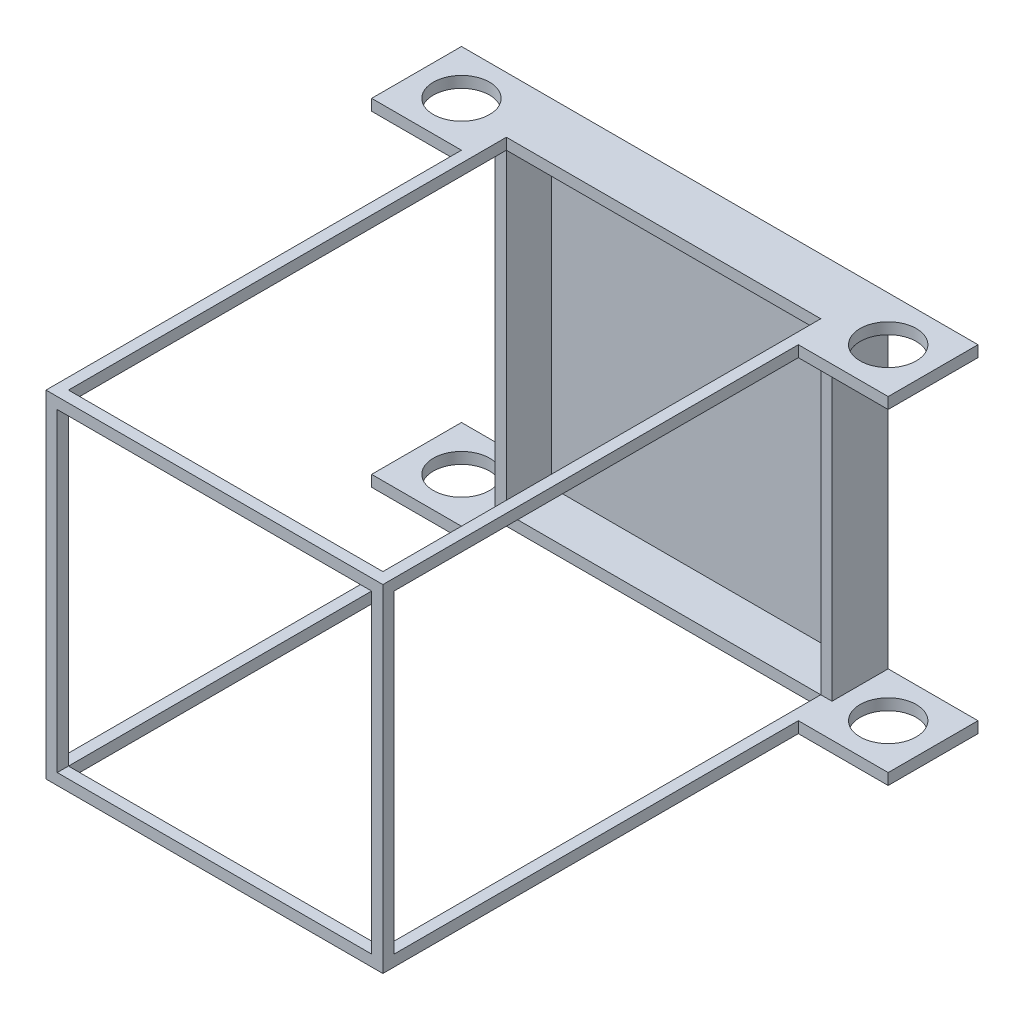
SolidWorks part; units mm, degrees
ref_plane "Спереди" through (0, 0, 0) normal (0, 0, 1) x (1, 0, 0)
ref_plane "Сверху" through (0, 0, 0) normal (0, 1, 0) x (1, 0, 0)
ref_plane "Справа" through (0, 0, 0) normal (1, 0, 0) x (0, 0, -1)
sketch "Эскиз1" plane through (0, 0, 0) normal (0, 0, 1) x (1, 0, 0)
  line L1 (5, 145) -> (145, 145)
  line L2 (5, 145) -> (5, 5)
  line L3 (5, 5) -> (145, 5)
  line L4 (145, 145) -> (145, 5)
  line L5 (0, 150) -> (150, 150)
  line L6 (0, 150) -> (0, 0)
  line L7 (0, 0) -> (150, 0)
  line L8 (150, 150) -> (150, 0)
  line L9 (150, 145) -> (190, 145)
  line L10 (150, 145) -> (150, 150)
  line L11 (150, 150) -> (190, 150)
  line L12 (190, 145) -> (190, 150)
  line L13 (0, 150) -> (-40, 150)
  line L14 (0, 150) -> (0, 145)
  line L15 (0, 145) -> (-40, 145)
  line L16 (-40, 150) -> (-40, 145)
  line L17 (150, 0) -> (190, 0)
  line L18 (150, 0) -> (150, 5)
  line L19 (150, 5) -> (190, 5)
  line L20 (190, 0) -> (190, 5)
  line L21 (0, 0) -> (-40, 0)
  line L22 (0, 0) -> (0, 5)
  line L23 (0, 5) -> (-40, 5)
  line L24 (-40, 0) -> (-40, 5)
  dimension "D1" = 150
  dimension "D2" = 150
  dimension "D3" = 5
  dimension "D4" = 5
  dimension "D5" = 5
  dimension "D6" = 5
  dimension "D7" = 5
  dimension "D8" = 40
  dimension "D9" = 40
  dimension "D10" = 5
  dimension "D11" = 40
  dimension "D12" = 5
  dimension "D13" = 40
  dimension "D14" = 5
extrude "Бобышка-Вытянуть2" add sketch "Эскиз1" along normal blind 5 contours L8 L5 L6 L7 L1 L4 L3 L2 region at (75, 147.8787, 0)
extrude "Бобышка-Вытянуть3" add sketch "Эскиз1<4>" along normal mid plane 40 contours L14 L15 L16 L13 | L22 L23 L24 L21 | L17 L20 L19 L18 | L11 L12 L9 L10
sketch "Эскиз1<4>" plane through (0, 0, 0) normal (0, 0, 1) x (1, 0, 0) same geometry as "Эскиз1"
sketch "Эскиз2" plane through (0, 0, 0) normal (0, -1, 0) x (1, 0, 0)
  line L0 (0, 20) -> (-40, 20) construction
  line L1 (-20, 20) -> (-20, -20) construction
  line L2 (0, -20) -> (-40, -20) construction
  circle A0 centre (-20, 0) radius 12.5
  point P8 (0, 0)
  dimension "D1" = 25
extrude "Вырез-Вытянуть1" cut sketch "Эскиз2" against normal through all
pattern_linear "Линейный массив1" count 2 spacing 190 along (1, 0, 0) of "Вырез-Вытянуть1"
sketch "Эскиз4" plane through (0, 0, 5) normal (0, 0, 1) x (1, 0, 0)
  line L1 (145, 5) -> (150, 5)
  line L2 (145, 5) -> (145, 0)
  line L3 (145, 0) -> (150, 0)
  line L4 (150, 5) -> (150, 0)
extrude "Бобышка-Вытянуть5" add sketch "Эскиз4" along normal blind 200
pattern_linear "Линейный массив2" count 2 spacing 145 along (0, 1, 0) count 2 spacing 145 along (-1, 0, 0) of "Бобышка-Вытянуть5"
pattern_linear "Линейный массив3" count 2 spacing 200 along (0, 0, 1) of "Бобышка-Вытянуть2"
sketch "Эскиз5" plane through (0, 0, 0) normal (0, 0, -1) x (-1, 0, 0)
  line L1 (-150, 150) -> (0, 150)
  line L2 (-150, 150) -> (-150, 0)
  line L3 (-150, 0) -> (0, 0)
  line L4 (0, 150) -> (0, 0)
extrude "Бобышка-Вытянуть6" add sketch "Эскиз5" along normal blind 20
sketch "Эскиз7" plane through (0, 0, 0) normal (0, 0, 1) x (1, 0, 0)
  line L0 (5, 145) -> (5, 5) construction
  line L1 (5, 5) -> (145, 5)
  line L2 (5, 5) -> (5, 145)
  line L3 (5, 145) -> (145, 145)
  line L4 (145, 5) -> (145, 145)
  line L5 (145, 145) -> (145, 5) construction
  line L8 (5, 145) -> (145, 145) construction
  point P8 (0, 0)
  point P9 (0, 0)
  dimension "D1" = 0
  dimension "D2" = 0
  dimension "D3" = 0
extrude "Вырез-Вытянуть3" cut sketch "Эскиз7" against normal blind 15
